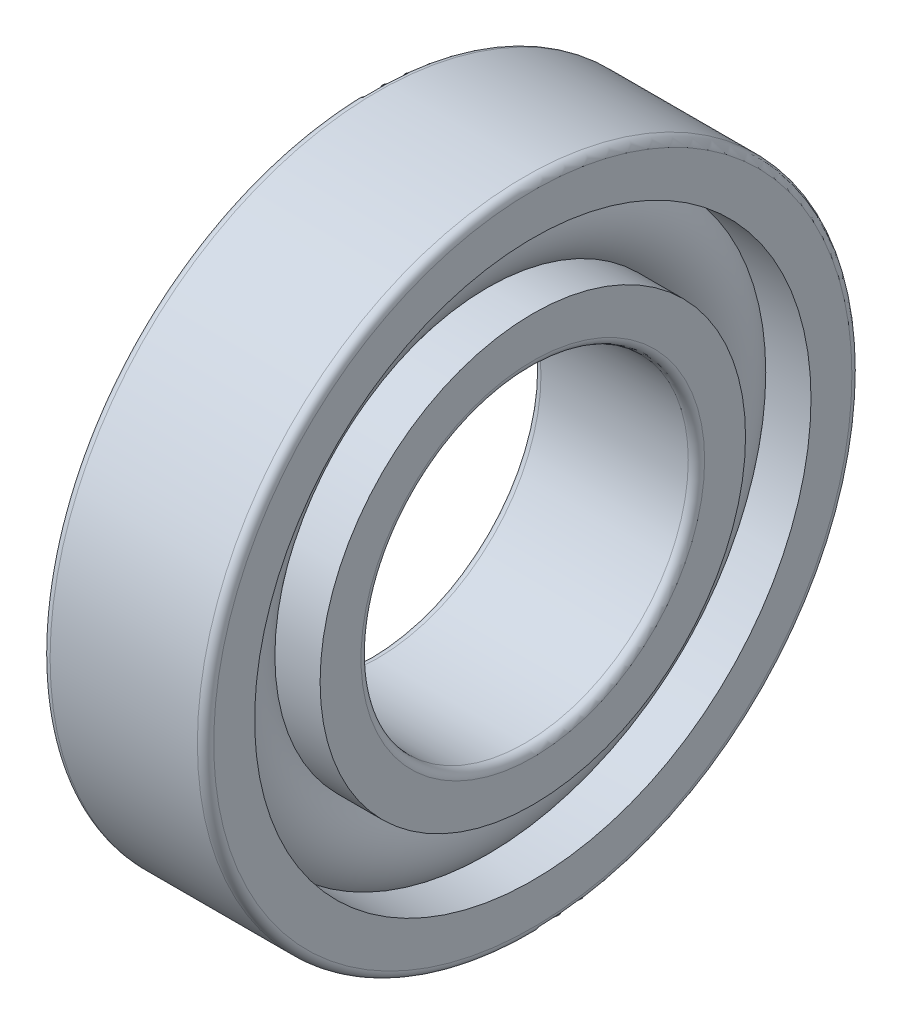
SolidWorks part; units mm, degrees
ref_plane "Plane1" through (0, 0, 0) normal (0, 0, 1) x (1, 0, 0)
ref_plane "Plane2" through (0, 0, 0) normal (0, 1, 0) x (1, 0, 0)
ref_plane "Plane3" through (0, 0, 0) normal (1, 0, 0) x (0, 0, -1)
sketch "Clipboard" plane through (0, 0, 0) normal (0, 0, 1) x (1, 0, 0)
  line L0 (-10, 0) -> (10, 0) construction
  line L1 (0, 0) -> (22.3471, -0.7804)
  line L2 (0, 0) -> (5.9963, 0.2094)
  line L3 (0, 0) -> (22.3471, -0.7804)
  line L4 (0, 0) -> (-22.3573, -0.3902)
  dimension "BallCLRad" = 6
sketch "CagSpiSke" plane through (0, 0, 0) normal (0, 0, 1) x (1, 0, 0)
  line L0 (0.12, 5.8) -> (0.12, 6.2)
  line L1 (0.12, 6.2) -> (-0.12, 6.2)
  line L2 (-0.12, 6.2) -> (-0.12, 5.8)
  line L3 (-0.12, 5.8) -> (0.12, 5.8)
  line L4 (-20.6375, 0) -> (20.6375, 0) construction
  line L5 (0, 0) -> (0, 23.7692) construction
  dimension "OD" = 12.4
  dimension "ID" = 11.6
revolve "CageSpine" add sketch "CagSpiSke" angle 0.001 about L4 reverse direction yes
ref_axis "Axis1" through (-50, 0, 0) along (1, 0, 0)
sketch "CagBalSke" plane through (0, 0, 0) normal (0, 0, 1) x (1, 0, 0)
  line L0 (-1.32, 6) -> (1.32, 6)
  line L1 (-1.905, 6) -> (1.905, 6) construction
  line L2 (-10, 0) -> (10, 0) construction
  line L3 (0, 0) -> (0, 24) construction
  arc A0 (1.32, 6) -> (-1.32, 6) centre (0, 6) cw
  dimension "BallCLRad" = 6
revolve "CageBall" [suppressed] add sketch "CagBalSke" angle 360 about L1 reverse direction yes
pattern_circular "CageBalls" [suppressed] count 2 every 180 about axis through (-50, 0, 0) along (1, 0, 0)
sketch "CagTrmODSke" plane through (0, 0, 0) normal (0, 0, 1) x (1, 0, 0)
  line L0 (1.321, 6.2) -> (1.321, 7.321)
  line L1 (1.321, 7.321) -> (-1.321, 7.321)
  line L2 (-1.321, 7.321) -> (-1.321, 6.2)
  line L3 (-1.321, 6.2) -> (1.321, 6.2)
  line L4 (-20.6375, 0) -> (20.6375, 0) construction
  line L5 (0, 0) -> (0, 25) construction
  dimension "Width" = 2.642
  dimension "ID" = 12.4
  dimension "OD" = 14.642
revolve "CageTrimOD" [suppressed] cut sketch "CagTrmODSke" angle 360 about L4 reverse direction yes
sketch "CagTrmIDSke" plane through (0, 0, 0) normal (0, 0, 1) x (1, 0, 0)
  line L0 (1.321, 4.681) -> (1.321, 5.8)
  line L1 (1.321, 5.8) -> (-1.321, 5.8)
  line L2 (-1.321, 5.8) -> (-1.321, 4.681)
  line L3 (-1.321, 4.681) -> (1.321, 4.681)
  line L4 (-20.6375, 0) -> (20.6375, 0) construction
  line L5 (0, 0) -> (0, 25) construction
  dimension "Width" = 2.642
  dimension "ID" = 9.362
  dimension "OD" = 11.6
revolve "CageTrimID" [suppressed] cut sketch "CagTrmIDSke" angle 360 about L4 reverse direction yes
sketch "BalSimSke" plane through (0, 0, 0) normal (0, 0, 1) x (1, 0, 0)
  line L0 (-10, 0) -> (10, 0) construction
  line L1 (-10, 6) -> (10, 6) construction
  line L2 (0, 0) -> (0, 23) construction
  circle A0 centre (0, 6) radius 1.2
  dimension "BallCLRad" = 6
  dimension "Ball_diameter" = 2.4
revolve "BallsSimplified" add sketch "BalSimSke" angle 360 about L0
sketch "BalDetSke" plane through (0, 0, 0) normal (0, 0, 1) x (1, 0, 0)
  line L0 (-1.2, 6) -> (1.2, 6)
  line L1 (-1.905, 6) -> (1.905, 6) construction
  line L2 (0, 0) -> (0, 25) construction
  arc A0 (1.2, 6) -> (-1.2, 6) centre (0, 6) cw
  dimension "BallCLRad" = 6
  dimension "Ball_diameter" = 2.4
revolve "BallDetailed" [suppressed] add sketch "BalDetSke" angle 360 about L1 reverse direction yes
sketch "InnRacSke" plane through (0, 0, 0) normal (0, 0, 1) x (1, 0, 0)
  line L0 (-0.8606, 5.2) -> (-2, 5.2)
  line L1 (-2, 5.2) -> (-2, 4.2)
  line L2 (-1.8, 4) -> (1.8, 4)
  line L3 (2, 4.2) -> (2, 5.2)
  line L4 (2, 5.2) -> (0.8606, 5.2)
  line L5 (-20.6375, 0) -> (20.6375, 0) construction
  line L6 (0, 0) -> (0, 30) construction
  arc A0 (-2, 4.2) -> (-1.8, 4) centre (-1.8, 4.2) ccw
  arc A1 (1.8, 4) -> (2, 4.2) centre (1.8, 4.2) ccw
  arc A2 (0.8606, 5.2) -> (-0.8606, 5.2) centre (0, 6) cw
  dimension "BallCLRad" = 6
  dimension "Fillet_radius" = 0.2
  dimension "Ball_diameter" = 2.35
  dimension "ID" = 8
  dimension "OD" = 10.4
  dimension "Width" = 4
revolve "InnerRace" add sketch "InnRacSke" angle 360 about L5 reverse direction yes
sketch "OutRacSke" plane through (0, 0, 0) normal (0, 0, 1) x (1, 0, 0)
  line L0 (-0.8606, 6.8) -> (-2, 6.8)
  line L1 (-2, 6.8) -> (-2, 7.8)
  line L2 (-1.8, 8) -> (1.8, 8)
  line L3 (2, 7.8) -> (2, 6.8)
  line L4 (2, 6.8) -> (0.8606, 6.8)
  line L5 (-20.6375, 0) -> (20.6375, 0) construction
  line L6 (0, 0) -> (0, 30) construction
  arc A0 (-2, 7.8) -> (-1.8, 8) centre (-1.8, 7.8) cw
  arc A1 (1.8, 8) -> (2, 7.8) centre (1.8, 7.8) cw
  arc A2 (0.8606, 6.8) -> (-0.8606, 6.8) centre (0, 6) ccw
  dimension "BallCLRad" = 6
  dimension "Fillet_radius" = 0.2
  dimension "Ball_diameter" = 2.35
  dimension "Width" = 4
revolve "OuterRace" add sketch "OutRacSke" angle 360 about L5 reverse direction yes
pattern_circular "BallsDetailed" [suppressed] count 2 every 180 about axis through (-50, 0, 0) along (1, 0, 0)
equation "\"BallCLRad@Clipboard\" = ( \"OD@OutRacSke\" + \"ID@InnRacSke\" ) / 4"
equation "\"BallCLRad@BalSimSke\" = \"BallCLRad@Clipboard\""
equation "\"BallCLRad@BalDetSke\" = \"BallCLRad@Clipboard\""
equation "\"BallCLRad@InnRacSke\" = \"BallCLRad@Clipboard\""
equation "\"BallCLRad@OutRacSke\" = \"BallCLRad@Clipboard\""
equation "\"Ball_diameter@InnRacSke\" = \"Ball_diameter@BalDetSke\" - 0.05"
equation "\"Ball_diameter@OutRacSke\" = \"Ball_diameter@BalDetSke\" - 0.05"
equation "\"Ball_diameter@BalSimSke\" = \"Ball_diameter@BalDetSke\""
equation "\"Width@OutRacSke\" = \"Width@InnRacSke\""
equation "\"Fillet_radius@OutRacSke\" = \"Fillet_radius@InnRacSke\""
equation "\"Max_count@Clipboard\" = int( 3.14159265 / atn(( \"Ball_diameter@BalDetSke\" / 2) / sqr( \"BallCLRad@Clipboard\"  *  \"BallCLRad@Clipboard\" - ( \"Ball_diameter@BalDetSke\" / 2) *  ( \"Ball_diameter@BalDetSke\" / 2))))"
equation "\"Max_count@Clipboard\" = ((sgn( \"Max_count@Clipboard\" - \"Count@Clipboard\" )-1)*( \"Max_count@Clipboard\" - \"Count@Clipboard\" ))/-2+ \"Count@Clipboard\""
equation "\"Count@BallsDetailed\" = int( \"Show_count@Clipboard\" ) "
equation "\"Count@BallsDetailed\" = ((sgn( \"Count@BallsDetailed\" - \"Max_count@Clipboard\" )-1)*( \"Count@BallsDetailed\" - \"Max_count@Clipboard\" ))/-2+ \"Max_count@Clipboard\""
equation "\"Count@BallsDetailed\" = ((sgn( \"Count@BallsDetailed\" - \"Min_count@Clipboard\" )+1)*( \"Count@BallsDetailed\" - \"Min_count@Clipboard\"))/2 +\"Min_count@Clipboard\""
equation "\"Angle@BallsDetailed\" = 360.0 / \"Max_count@Clipboard\""
equation "\"BallCLRad@CagBalSke\" = \"BallCLRad@Clipboard\""
equation "\"Count@CageBalls\" = \"Count@BallsDetailed\""
equation "\"Angle@CageBalls\" = \"Angle@BallsDetailed\""
equation "\"Angle@CageSpine\" =  \"Angle@CageBalls\" * ( \"Count@CageBalls\" -1 + int( \"Count@CageBalls\" / \"Max_count@Clipboard\" ) )  + 0.001 -  int( \"Count@CageBalls\" / \"Max_count@Clipboard\" ) * 0.001"
equation "\"Angle@CageSpine\" =  \"Angle@CageSpine\" * int( \"Min_count@Clipboard\" / 2) + int(1 / \"Min_count@Clipboard\")  * 0.001"
equation "\"CageWallOD@CagBalSke\" =  \"Ball_diameter@BalDetSke\" * 1.1"
equation "\"Thickness@CagSpiSke\" =  \"Ball_diameter@BalDetSke\" * 0.1"
equation "\"OD@CagTrmODSke\" = \"BallCLRad@Clipboard\" * 2 + \"CageWallOD@CagBalSke\" + 0.002"
equation "\"ID@CagTrmODSke\" = \"BallCLRad@Clipboard\" * 2 + \"Ball_diameter@BalDetSke\" / 6"
equation "\"OD@CagTrmIDSke\" = \"BallCLRad@Clipboard\" * 2 - \"Ball_diameter@BalDetSke\" / 6"
equation "\"ID@CagTrmIDSke\" = \"BallCLRad@Clipboard\" * 2 - \"CageWallOD@CagBalSke\" + 0.002"
equation "\"OD@CagSpiSke\" = \"ID@CagTrmODSke\""
equation "\"ID@CagSpiSke\" = \"OD@CagTrmIDSke\""
equation "\"Width@CagTrmODSke\" = \"CageWallOD@CagBalSke\" + 0.002"
equation "\"Width@CagTrmIDSke\" = \"CageWallOD@CagBalSke\" + 0.002"
